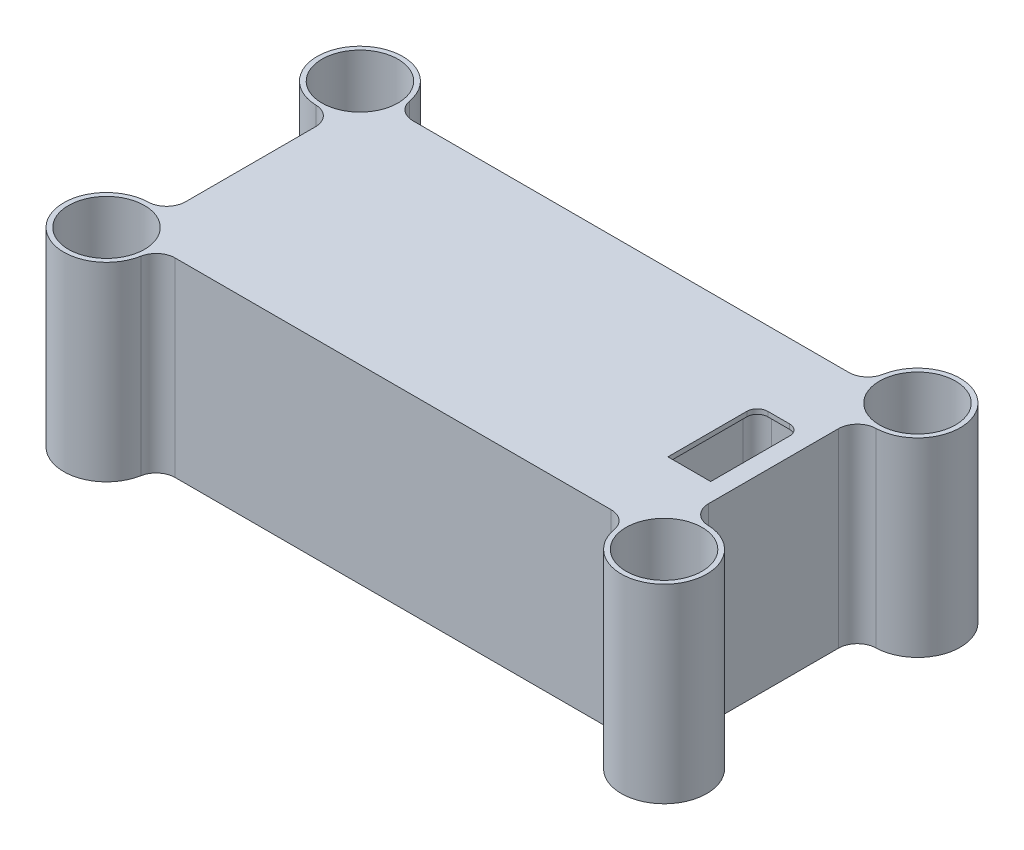
SolidWorks part; units mm, degrees
ref_plane "Front Plane" through (0, 0, 0) normal (0, 0, 1) x (1, 0, 0)
ref_plane "Top Plane" through (0, 0, 0) normal (0, 1, 0) x (1, 0, 0)
ref_plane "Right Plane" through (0, 0, 0) normal (1, 0, 0) x (0, 0, -1)
sketch "Sketch1" plane through (0, 0, 0) normal (0, 1, 0) x (1, 0, 0)
  line L0 (0, 12.5) -> (0, -12.5) construction
  line L1 (-27.5, 12.5) -> (27.5, 12.5)
  line L2 (-27.5, 12.5) -> (-27.5, -12.5)
  line L3 (-27.5, -12.5) -> (27.5, -12.5)
  line L4 (27.5, 12.5) -> (27.5, -12.5)
  line L5 (-27.5, 12.5) -> (27.5, -12.5) construction
  line L6 (-27.5, -12.5) -> (27.5, 12.5) construction
  line L7 (-27.5, 0) -> (27.5, 0) construction
  line L8 (-24.8207, 13.3276) -> (-24.8207, 12.5)
  line L9 (-29.3207, 8.8276) -> (-27.5, 8.8276)
  line L10 (24.8207, 13.3276) -> (24.8207, 12.5)
  line L11 (29.3207, 8.8276) -> (27.5, 8.8276)
  line L12 (29.3207, -8.8276) -> (27.5, -8.8276)
  line L13 (24.8207, -13.3276) -> (24.8207, -12.5)
  line L14 (-24.8207, -13.3276) -> (-24.8207, -12.5)
  line L15 (-29.3207, -8.8276) -> (-27.5, -8.8276)
  circle A0 centre (-29.3207, 13.3276) radius 2
  circle A1 centre (-29.3207, 13.3276) radius 4.5
  circle A2 centre (29.3207, 13.3276) radius 2
  circle A3 centre (29.3207, 13.3276) radius 4.5
  circle A4 centre (29.3207, -13.3276) radius 2
  circle A5 centre (29.3207, -13.3276) radius 4.5
  circle A6 centre (-29.3207, -13.3276) radius 2
  circle A7 centre (-29.3207, -13.3276) radius 4.5
  point P0 (0, 0)
  dimension "D3" = 4
  dimension "D4" = 9
  dimension "D1" = 25
  dimension "D2" = 55
extrude "Boss-Extrude1" add sketch "Sketch1" along normal blind 20 contours A7 L3 A6 L2 | L3 A7 L14 | A7 L2 L3 | L15 A7 L2 | L2 A7 L3 A5 L4 A3 L1 A1 | A1 L9 L2 | A1 L2 A0 L1 | L2 A1 L1 | A1 L1 L8 | L11 A3 L4 | L1 A3 L10 | A3 L4 L1 | A3 L1 A2 L4 | A5 L12 L4 | A5 L3 L13 | L4 A5 L3 | A5 L4 A4 L3 region at (0, 0, 0) region at (-24.8437, 0, -12.7065) region at (24.8437, 0, -12.7065) region at (-26.4801, 0, -11.2313) region at (-26.1987, 0, -12.6273) region at (24.9667, 0, -12.9238) region at (26.4801, 0, -11.2313) region at (-27.9512, 0, -8.9421) region at (27.9512, 0, -8.9421) region at (-27.9512, 0, 8.9421) region at (27.9512, 0, 8.9421) region at (-26.4801, 0, 11.2313) region at (-27.6273, 0, 10.8562) region at (28.4166, 0, 9.0494) region at (26.4801, 0, 11.2313) region at (-24.8437, 0, 12.7065) region at (24.8437, 0, 12.7065)
sketch "Sketch2" plane through (0, 20, 0) normal (0, 1, 0) x (1, 0, 0)
  line L0 (0, 12.5) -> (0, -12.5) construction
  line L1 (-24.8207, 12.5) -> (24.8207, 12.5) construction
  line L2 (-24.8207, -12.5) -> (24.8207, -12.5) construction
  line L3 (-27.5, 0) -> (27.5, 0) construction
  line L4 (-27.5, 8.8276) -> (-27.5, -8.8276) construction
  line L5 (27.5, 8.8276) -> (27.5, -8.8276) construction
  circle A0 centre (-29.3207, 13.3276) radius 4
  arc A1 (-24.8207, 13.3276) -> (-29.3207, 8.8276) centre (-29.3207, 13.3276) ccw construction
  circle A2 centre (29.3207, 13.3276) radius 4
  circle A3 centre (29.3207, -13.3276) radius 4
  circle A4 centre (-29.3207, -13.3276) radius 4
  dimension "D1" = 0.5
extrude "Cut-Extrude1" cut sketch "Sketch2" against normal offset from surface (18.5 mm away) 1.5 up to face at (0, 0, 0)
sketch "Sketch3" plane through (0, 20, 0) normal (0, 1, 0) x (1, 0, 0)
  line L0 (-27.5, 0) -> (27.5, 0) construction
  line L1 (-27.5, 8.8276) -> (-27.5, -8.8276) construction
  line L2 (27.5, 8.8276) -> (27.5, -8.8276) construction
  line L3 (23.35, 12.5) -> (23.35, -12.5) construction
  line L4 (-24.8207, 12.5) -> (24.8207, 12.5) construction
  line L5 (-24.8207, -12.5) -> (24.8207, -12.5) construction
  line L7 (22.2, 5.1) -> (24.5, 5.1)
  line L8 (20.7, 3.6) -> (20.7, -5.1)
  line L9 (20.7, -5.1) -> (26, -5.1)
  line L10 (26, 3.6) -> (26, -5.1)
  line L11 (20.7, 5.1) -> (26, -5.1) construction
  line L12 (20.7, -5.1) -> (26, 5.1) construction
  arc A0 (24.5, 5.1) -> (26, 3.6) centre (24.5, 3.6) cw
  arc A1 (22.2, 5.1) -> (20.7, 3.6) centre (22.2, 3.6) ccw
  point P12 (23.35, 0)
  dimension "D4" = 1.5
  dimension "D1" = 1.5
  dimension "D2" = 10.2
  dimension "D3" = 5.3
extrude "Cut-Extrude2" cut sketch "Sketch3" against normal up to next from offset 0.5 offset against normal yes
sketch "Sketch5" plane through (0, 0, 0) normal (0, -1, 0) x (1, 0, 0)
  line L0 (-27.5, 0) -> (-26, 0) construction
  line L1 (26, -11) -> (-26, -11)
  line L2 (26, -11) -> (26, 11)
  line L3 (26, 11) -> (-26, 11)
  line L4 (-26, -11) -> (-26, 11)
  line L5 (26, -11) -> (-26, 11) construction
  line L6 (26, 11) -> (-26, -11) construction
  line L7 (-27.5, -8.8276) -> (-27.5, 8.8276) construction
  line L8 (0, 11) -> (0, 12.5) construction
  line L9 (-24.8207, 12.5) -> (24.8207, 12.5) construction
  line L10 (19.2, 11) -> (19.2, -11)
  line L11 (19.2, 0) -> (20.7, 0) construction
  line L13 (19.2, 6.6) -> (26, 6.6)
  line L14 (23.35, 5.1) -> (23.35, 6.6) construction
  line L16 (19.2, -6.6) -> (26, -6.6)
  line L17 (26, 5.1) -> (20.7, 5.1) construction
  line L18 (20.7, 5.1) -> (20.7, -3.6) construction
  point P0 (0, 0)
  point P28 (0, 0)
  point P29 (0, 0)
  dimension "D1" = 1.5
extrude "Cut-Extrude4" cut sketch "Sketch5" against normal offset from surface (18.5 mm away) 1.5 contours L10 L3 L4 L1 | L10 L13 L2 L3 | L16 L10 L1 L2 region at (22.6, 0, -8.8) region at (-3.4, 0, 0) region at (22.6, 0, 8.8) up to face at (29.3207, 20, -17.3276)
sketch "Sketch7" plane through (0, 19.5, 0) normal (0, -1, 0) x (1, 0, 0)
  line L8 (25.6, -3.6) -> (25.6, 4.7)
  line L9 (25.6, 4.7) -> (21.1, 4.7)
  line L10 (21.1, 4.7) -> (21.1, -3.6)
  line L11 (22.2, -4.7) -> (24.5, -4.7)
  line L12 (25.6, -3.6) -> (25.6, 4.7)
  line L13 (25.6, 4.7) -> (21.1, 4.7)
  line L14 (21.1, 4.7) -> (21.1, -3.6)
  line L15 (22.2, -4.7) -> (24.5, -4.7)
  arc A4 (21.1, -3.6) -> (22.2, -4.7) centre (22.2, -3.6) ccw
  arc A5 (24.5, -4.7) -> (25.6, -3.6) centre (24.5, -3.6) ccw
  arc A6 (21.1, -3.6) -> (22.2, -4.7) centre (22.2, -3.6) ccw
  arc A7 (24.5, -4.7) -> (25.6, -3.6) centre (24.5, -3.6) ccw
  dimension "D1" = 0.4
extrude "Cut-Extrude6" cut sketch "Sketch7" against normal up to next
sketch "Sketch8" plane through (0, 0, 0) normal (0, -1, 0) x (1, 0, 0)
  line L1 (19.2, 6.6) -> (26, 6.6)
  line L2 (19.2, 6.6) -> (19.2, -6.6)
  line L3 (19.2, -6.6) -> (26, -6.6)
  line L4 (26, 6.6) -> (26, -6.6)
extrude "Cut-Extrude7" cut sketch "Sketch8" against normal offset from surface (8.8 mm away) 10.7 up to face at (23.35, 19.5, -1.2759)
fillet "Fillet1" radius 2 8 edges at (-24.8207, 10, 12.5) (27.5, 10, -8.8276) (27.5, 10, 8.8276) (-24.8207, 10, -12.5) (24.8207, 10, -12.5) (-27.5, 10, 8.8276) (24.8207, 10, 12.5) (-27.5, 10, -8.8276)
